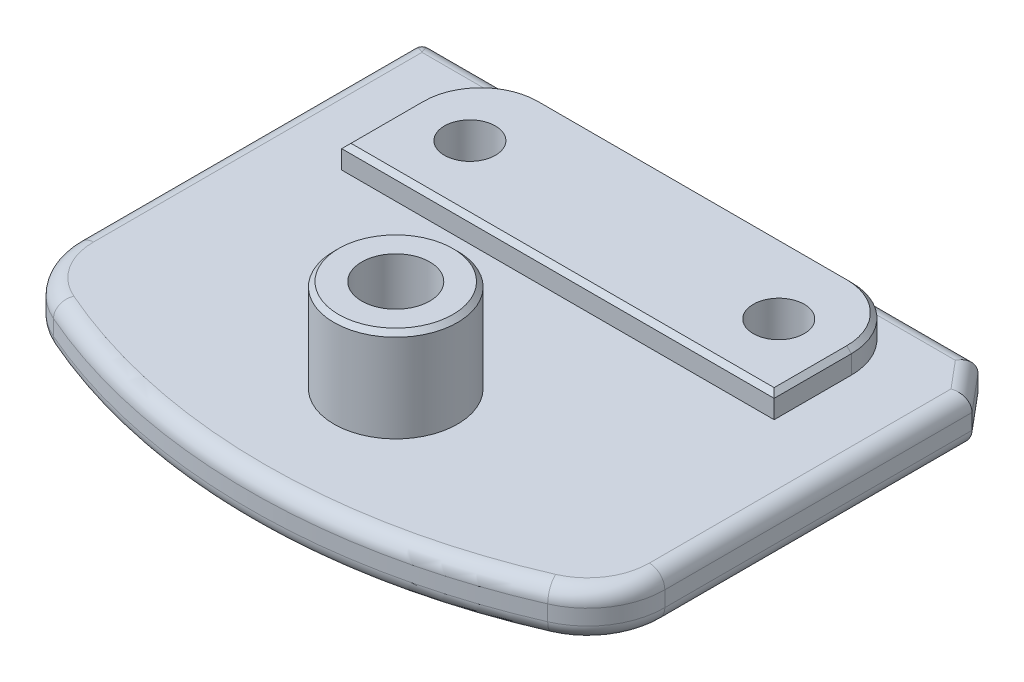
SolidWorks part; units mm, degrees
material "6061-T6 (SS)"
ref_plane "정면" through (0, 0, 0) normal (0, 0, 1) x (1, 0, 0)
ref_plane "윗면" through (0, 0, 0) normal (0, 1, 0) x (1, 0, 0)
ref_plane "우측면" through (0, 0, 0) normal (1, 0, 0) x (0, 0, -1)
sketch "스케치1" plane through (0, 0, 0) normal (0, 1, 0) x (1, 0, 0)
  line L0 (-10, 14.8) -> (10, 14.8) construction
  line L1 (0, 14.8) -> (0, 0) construction
  line L2 (-19, 10.5) -> (19, 10.5)
  line L3 (-10, 19.5) -> (10, 19.5)
  line L4 (0, 14.8) -> (0, 19.5) construction
  line L5 (-14, 15.5) -> (-14, 10.5)
  line L6 (14, 15.5) -> (14, 10.5)
  line L7 (-19, 20.7) -> (19, 20.7)
  line L8 (0, 19.5) -> (0, 20.7) construction
  line L11 (-19, 10.5) -> (-19, -4.6994)
  line L12 (-19, -9.5) -> (19, -9.5) construction
  line L13 (19, -4.6994) -> (19, 10.5)
  line L14 (-14, 10.5) -> (-19, 10.5)
  line L16 (-19, 10.5) -> (-19, 20.7)
  line L17 (19, 10.5) -> (19, 20.7)
  circle A0 centre (0, 0) radius 2.2
  circle A1 centre (-10, 14.8) radius 1.65
  circle A2 centre (10, 14.8) radius 1.65
  arc A3 (10, 19.5) -> (14, 15.5) centre (10, 15.5) cw
  arc A4 (-10, 19.5) -> (-14, 15.5) centre (-10, 15.5) ccw
  arc A7 (-19, -4.6994) -> (19, -4.6994) centre (0, 30.5) ccw
  circle A8 centre (0, 0) radius 4
  point P10 (0, 10.5)
  point P18 (14, 19.5)
  point P21 (-14, 19.5)
  point P29 (-19, 20.7)
  dimension "D3" = 3.3
  dimension "D8" = 4
  dimension "D10" = 4.4
  dimension "D12" = 80
  dimension "D13" = 8
  dimension "D1" = 14.8
  dimension "D2" = 20
  dimension "D4" = 10.5
  dimension "D5" = 38
  dimension "D6" = 28
  dimension "D7" = 9
  dimension "D9" = 1.2
  dimension "D11" = 20
extrude "보스-돌출1" add sketch "스케치1" along normal blind 1.5 contours L3 A4 L5 L2 L6 A3 A1 A2 region at (0, 0, -14.9064)
extrude "보스-돌출2" add sketch "스케치1<3>" against normal blind 3 contours L7 L2 L5 A4 L3 A3 L6 | L3 A4 L5 L2 L6 A3 A1 A2 | L11 A7 L13 L2 A8 | L14 | A8 A0 region at (-18.6065, 0, -15.6) region at (-16.5, 0, -10.0706) region at (0, 0, -14.9064) region at (-3.8869, 0, 0)
sketch "스케치1<3>" plane through (0, 0, 0) normal (0, 1, 0) x (1, 0, 0) same geometry as "스케치1"
extrude "보스-돌출3" add sketch "스케치1<5>" along normal blind 6 contours A8 A0 region at (-3.8869, 0, 0)
sketch "스케치1<5>" plane through (0, 0, 0) normal (0, 1, 0) x (1, 0, 0) same geometry as "스케치1"
fillet "필렛6" radius 0.5 1 edges at (-19, -1.5, -20.7)
fillet "필렛3" radius 5 2 edges at (-19, -1.5, 4.6994) (19, -1.5, 4.6994)
chamfer "모따기9" distance 2 angle 50 1 edges at (19, -1.5, -20.7) first distance on face at (0.25, -1.5, -20.7)
fillet "필렛5" radius 1 16 edges at (-0.75, 0, -20.7) (19, 0, -8.3692) (18.1833, 0, 4.3166) (0, 0, 9.5) (-18.1833, 0, 4.3166) (-19, 0, -9.311) (18.1833, -3, 4.3166) (-0.75, -3, -20.7) (-19, -3, -9.311) (-18.1833, -3, 4.3166) (0, -3, 9.5) (19, -3, -8.3692) (-18.8536, 0, -20.5536) (-18.8536, -3, -20.5536) (18, 0, -19.5082) (18, -3, -19.5082)
chamfer "모따기2" distance 0.3 angle 45 1 edges at (0, 6, 4)
chamfer "모따기3" distance 0.3 angle 45 6 edges at (14, 1.5, -13) (12.8284, 1.5, -18.3284) (0, 1.5, -19.5) (0, 1.5, -10.5) (-14, 1.5, -13) (-12.8284, 1.5, -18.3284)
sketch "스케치2" plane through (0, -3, 0) normal (0, -1, 0) x (1, 0, 0)
  circle A0 centre (0, 0) radius 4
  dimension "D1" = 8
extrude "컷-돌출1" cut sketch "스케치2" against normal blind 2
chamfer "모따기4" distance 0.3 angle 45 3 edges at (-10, -3, -13.15) (10, -3, -13.15) (0, -3, -4)
